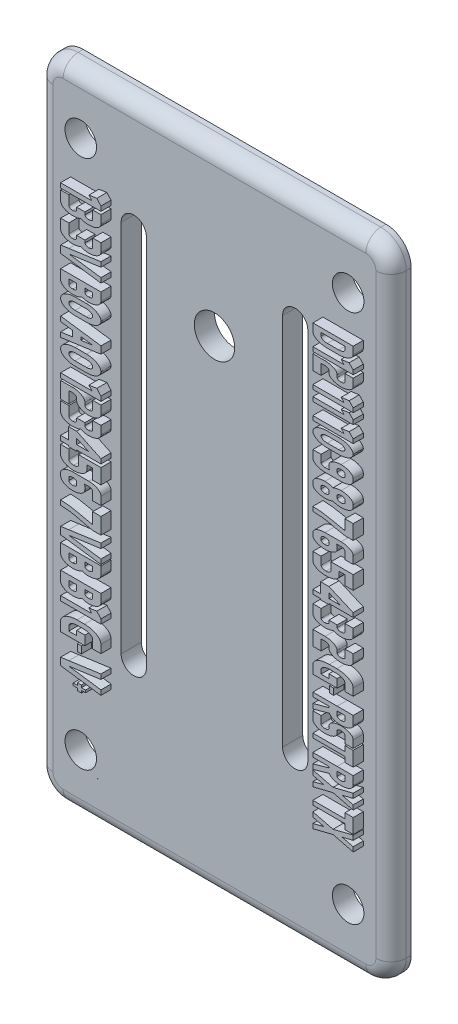
SolidWorks part; units mm, degrees
ref_plane "Front Plane" through (0, 0, 0) normal (0, 0, 1) x (1, 0, 0)
ref_plane "Top Plane" through (0, 0, 0) normal (0, 1, 0) x (1, 0, 0)
ref_plane "Right Plane" through (0, 0, 0) normal (1, 0, 0) x (0, 0, -1)
sketch "Sketch1" plane through (0, 0, 0) normal (0, 0, 1) x (1, 0, 0)
  line L1 (0, 32) -> (0, -32) construction
  line L2 (16.455, 32) -> (-16.455, 32) construction
  line L3 (-16.455, -32) -> (16.455, -32) construction
  line L4 (17.455, 31) -> (17.455, -31) construction
  line L5 (17.455, 0) -> (-17.455, 0) construction
  line L6 (-17.455, 31) -> (-17.455, -31) construction
  line L7 (17.7124, 32) -> (16.455, 32) construction
  line L8 (-15, -32) -> (15, -32)
  line L9 (-17.5, -29.5) -> (-17.5, 29.5)
  line L10 (-15, 32) -> (15, 32)
  line L11 (17.5, -29.5) -> (17.5, 29.5)
  line L12 (0, 32) -> (0, -32) construction
  line L13 (-17.5, 0) -> (17.5, 0) construction
  arc A0 (-15, -32) -> (-17.5, -29.5) centre (-15, -29.5) cw
  arc A1 (15, -32) -> (17.5, -29.5) centre (15, -29.5) ccw
  arc A2 (15, 32) -> (17.5, 29.5) centre (15, 29.5) cw
  arc A3 (-17.5, 29.5) -> (-15, 32) centre (-15, 29.5) cw
  circle A4 centre (-11.5563, -27.8796) radius 0.0197
  circle A5 centre (-13.25, -26.25) radius 1.5625
  circle A6 centre (-13.25, 26.25) radius 1.5625
  circle A7 centre (-13.25, -26.25) radius 2.37 construction
  circle A8 centre (13.25, -26.25) radius 1.5625
  circle A9 centre (13.25, 26.25) radius 1.5625
  point P12 (0, 0)
  point P25 (17.5, 32)
  dimension "D3" = 2.5
  dimension "D4" = 0.0393
  dimension "D5" = 3.125
  dimension "D1" = 35
  dimension "D2" = 64
  dimension "D6" = 11.5563
  dimension "D7" = 27.8796
extrude "Boss-Extrude1" add sketch "Sketch1" along normal blind 2
sketch "Sketch2" plane through (0, 0, 2) normal (0, 0, 1) x (1, 0, 0)
  line L0 (-13.6273, 22.1478) -> (-13.6273, -16.8522) construction
  line L1 (-11.75, 22.1478) -> (-15.5046, 22.1478) construction
  line L2 (-15.5046, -16.8522) -> (-11.75, -16.8522) construction
  line L4 (0, 2.52) -> (-13.6273, 2.52) construction
  line L6 (-8, -16) -> (-8, 21.04) construction
  line L9 (0, -16.85) -> (0, 21.89) construction
  line L12 (-9.25, -16) -> (-9.25, 21.04)
  line L15 (-6.75, -16) -> (-6.75, 21.04)
  line L16 (8, -16) -> (8, 21.04) construction
  line L17 (9.25, -16) -> (9.25, 21.04)
  line L18 (6.75, -16) -> (6.75, 21.04)
  line L19 (17.5, -29.5) -> (17.5, 29.5) construction
  line L20 (-15, -32) -> (15, -32) construction
  line L21 (-13.6273, 2.6478) -> (0, 2.6478) construction
  arc A4 (-9.25, -16) -> (-6.75, -16) centre (-8, -16) ccw
  arc A5 (-6.75, 21.04) -> (-9.25, 21.04) centre (-8, 21.04) ccw
  arc A6 (9.25, -16) -> (6.75, -16) centre (8, -16) cw
  arc A7 (6.75, 21.04) -> (9.25, 21.04) centre (8, 21.04) cw
  point P11 (8, 2.52)
  point P14 (-8, 2.52)
  dimension "D3" = 17.5
  dimension "D4" = 16
  dimension "D2" = 9.5
  dimension "D1" = 2.5
  dimension "D5" = 34.52
fillet "Fillet1" radius 1.5 8 edges at (-16.7678, -31.2678, 2) (0, -32, 2) (16.7678, -31.2678, 2) (16.7678, 31.2678, 2) (17.5, 0, 2) (-16.7678, 31.2678, 2) (-17.5, 0, 2) (0, 32, 2)
sketch "Sketch3" plane through (0, 0, 2) normal (0, 0, 1) x (1, 0, 0)
  line L0 (16, -29.5) -> (16, 29.5) construction
  line L6 (-8.88, 26.4) -> (8.88, 26.4) construction
  circle A0 centre (0, 15.9) radius 2
  dimension "D1" = 10.5
  dimension "D2" = 4
  dimension "D3" = 16
extrude "Cut-Extrude2" cut sketch "Sketch3" against normal through all contours A0
extrude "Cut-Extrude3" cut sketch "Sketch2" against normal through all
sketch "Sketch4" plane through (0, 0, 2) normal (0, 0, 1) x (1, 0, 0)
  line L0 (-14.25, 23) -> (-14.25, -20.05) construction
  line L1 (10.75, 23) -> (10.75, -20.05) construction
  line L4 (-15, -30.5) -> (15, -30.5) construction
  line L5 (9.25, -16) -> (9.25, 21.04) construction
  text T0 "13 3V B0 A0 123456 7 VB B1 G- V+" font "BANSED" height 4
  text T1 "D12 11 10 9 8 7 6 5 4 3 2 G- RST RX TX" font "BANSED" height 4
  point P8 (0, 0)
  dimension "D1" = 53.5
  dimension "D2" = 10.45
  dimension "D3" = 30.5
  dimension "D4" = 5
  dimension "D5" = 1.5
  dimension "D6" = 9.25
extrude "Boss-Extrude4" add sketch "Sketch4" along normal blind 1
